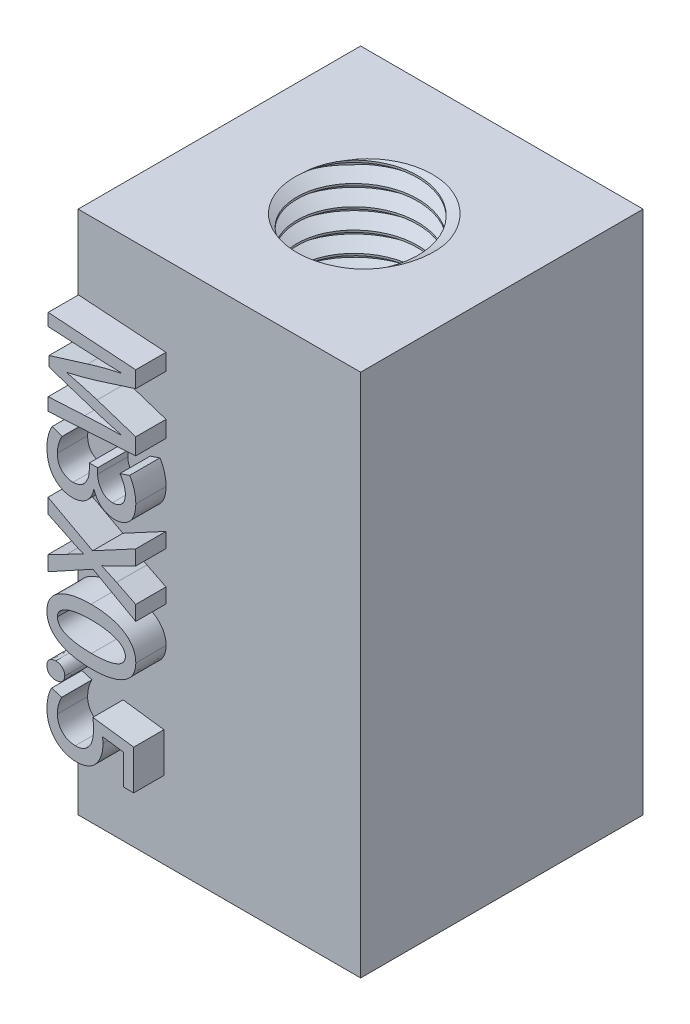
SolidWorks part; units mm, degrees
ref_plane "Alzado" through (0, 0, 0) normal (0, 0, 1) x (1, 0, 0)
ref_plane "Planta" through (0, 0, 0) normal (0, 1, 0) x (1, 0, 0)
ref_plane "Vista lateral" through (0, 0, 0) normal (1, 0, 0) x (0, 0, -1)
sketch "Croquis1" plane through (0, 0, 0) normal (0, 1, 0) x (1, 0, 0)
  line L1 (-3.5, 3.5) -> (3.5, 3.5)
  line L2 (-3.5, 3.5) -> (-3.5, -3.5)
  line L3 (-3.5, -3.5) -> (3.5, -3.5)
  line L4 (3.5, 3.5) -> (3.5, -3.5)
  line L5 (-3.5, 3.5) -> (3.5, -3.5) construction
  line L6 (-3.5, -3.5) -> (3.5, 3.5) construction
  circle A0 centre (0, 0) radius 1.5
  point P0 (0, 0)
  dimension "D1" = 3
  dimension "7" = 7
extrude "Saliente-Extruir1" add sketch "Croquis1" along normal blind 13
sketch "Croquis2" plane through (0, 0, 3.5) normal (0, 0, 1) x (1, 0, 0)
  text T0 "M3X0.5" font "@Adobe Heiti Std R" height in points 7
split line "Línea de partición1"
extrude "Saliente-Extruir2" add sketch "Croquis2<2>" along normal blind 0.75
sketch "Croquis2<2>" plane through (0, 0, 3.5) normal (0, 0, 1) x (1, 0, 0) same geometry as "Croquis2"
thread "Rosca1" pitch 0.6 method cut profile "Perfil de rosca1" start angle 0, offset 1, length 11, pitch 0.5, diameter 3
ref_plane "Plano1" through (-1.5, 14, 0) normal (0, 0, 1) x (-1, 0, 0)
sketch "Perfil de rosca1" plane through (-1.5, 14, 0) normal (0, 0, 1) x (-1, 0, 0)
  line L0 (0, 0) -> (0, 0.6) construction
  line L1 (0, 0) -> (0.3248, 0.1875)
  line L2 (0.3248, 0.1875) -> (0.3248, 0.2625)
  line L3 (0.3248, 0.2625) -> (0, 0.45)
  line L4 (0.3248, 0.225) -> (0, 0.225) construction
  line L11 (0, 0) -> (0, 0.45)
  point P2 (0, 0)
  dimension "Pitch" = 0.6
  dimension "Profile_Angle" = 60
  dimension "Profile_Land" = 0.075
  dimension "Profile_Height" = 0.3248
